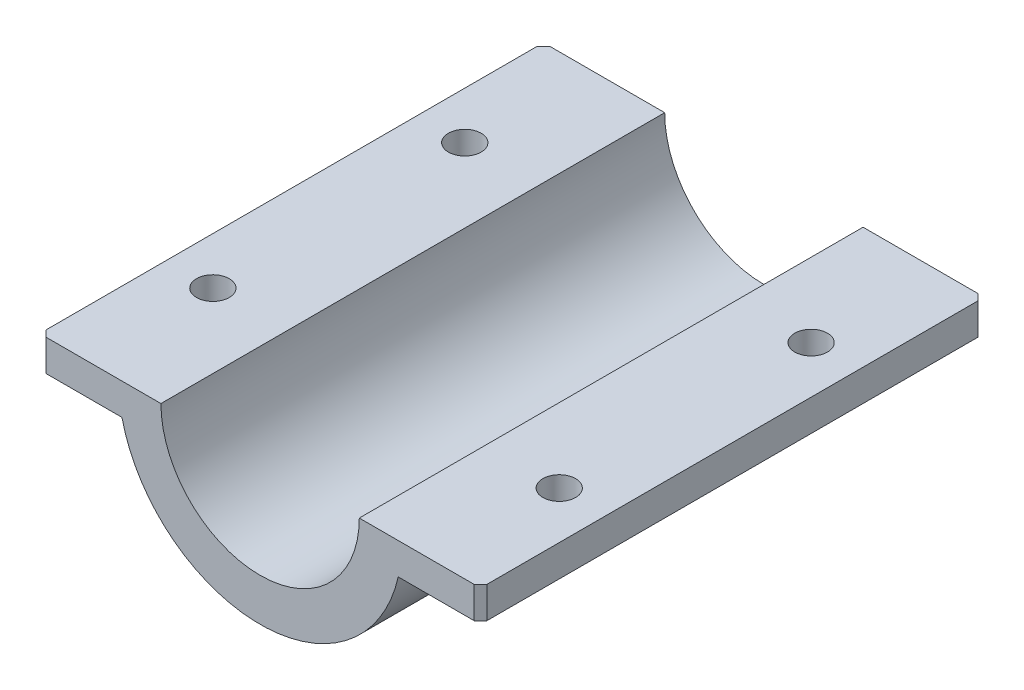
SolidWorks part; units mm, degrees
ref_plane "前视基准面" through (0, 0, 0) normal (0, 0, 1) x (1, 0, 0)
ref_plane "上视基准面" through (0, 0, 0) normal (0, 1, 0) x (1, 0, 0)
ref_plane "右视基准面" through (0, 0, 0) normal (1, 0, 0) x (0, 0, -1)
sketch "草图1" plane through (0, 0, 0) normal (0, 0, 1) x (1, 0, 0)
  line L0 (0, -15.75) -> (0, -22.5) construction
  line L1 (0, -22.5) -> (35, -22.5) construction
  line L2 (35, -22.5) -> (35, 0) construction
  line L3 (35, 0) -> (15.75, 0)
  line L5 (-35, -22.5) -> (0, -22.5) construction
  line L6 (-15.75, 0) -> (-35, 0)
  line L7 (-35, 0) -> (-35, -22.5) construction
  line L8 (-35, 0) -> (-35, -5)
  line L9 (-35, -5) -> (-21.9374, -5)
  line L10 (35, -5) -> (21.9374, -5)
  line L11 (35, 0) -> (35, -5)
  arc A0 (-15.75, 0) -> (15.75, 0) centre (0, 0) ccw
  arc A1 (-21.9374, -5) -> (21.9374, -5) centre (0, 0) ccw
  dimension "D1" = 5
  dimension "D3" = 22.5
  dimension "D4" = 15.75
  dimension "D2" = 35
extrude "凸台-拉伸1" add sketch "草图1" along normal mid plane 80
sketch "草图2" plane through (0, -5, 0) normal (0, -1, 0) x (-1, 0, 0)
  line L0 (35, -40) -> (35, -20) construction
  line L1 (35, -40) -> (35, 40) construction
  line L2 (35, -20) -> (27.5, -20) construction
  line L3 (0, 0) -> (0, -10) construction
  line L4 (0, 0) -> (10, 0) construction
  circle A0 centre (27.5, -20) radius 2.6
  circle A1 centre (27.5, 20) radius 2.6
  circle A2 centre (-27.5, -20) radius 2.6
  circle A3 centre (-27.5, 20) radius 2.6
extrude "切除-拉伸1" cut sketch "草图2" against normal blind 10
chamfer "倒角1" distance 1 angle 45 4 edges at (-35, -2.5, -40) (35, -2.5, -40) (35, -2.5, 40) (-35, -2.5, 40)
